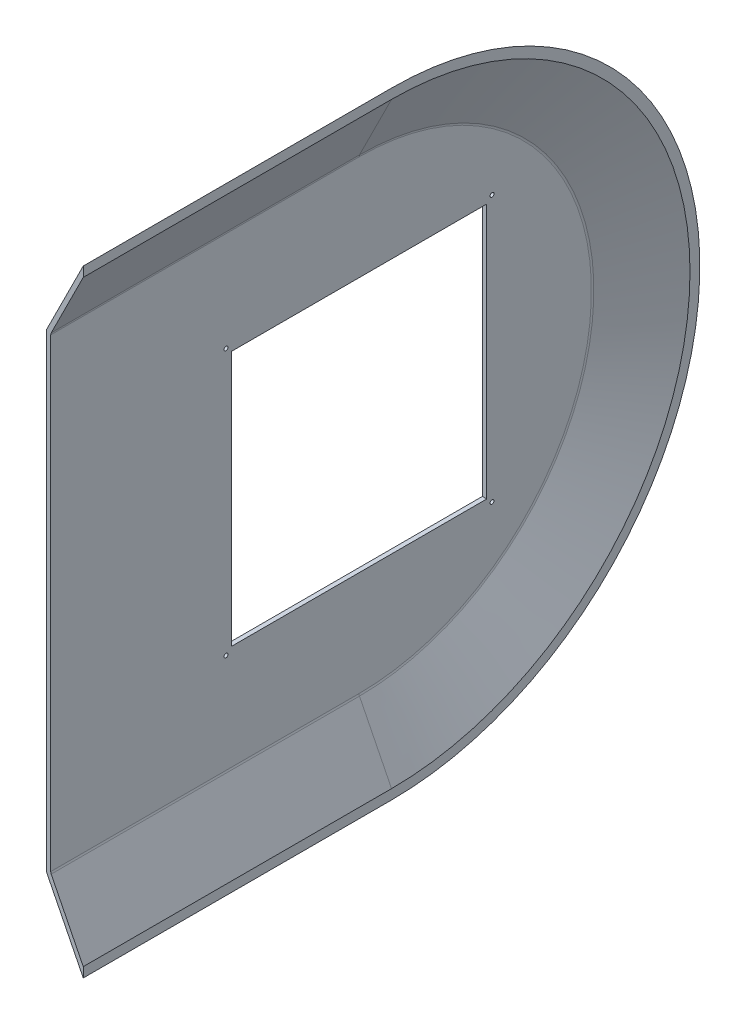
SolidWorks part; units mm, degrees
ref_plane "Plan de face" through (0, 0, 0) normal (0, 0, 1) x (1, 0, 0)
ref_plane "Plan de dessus" through (0, 0, 0) normal (0, 1, 0) x (1, 0, 0)
ref_plane "Plan de droite" through (0, 0, 0) normal (1, 0, 0) x (0, 0, -1)
sketch "Esquisse2" plane through (0, 0, 0) normal (0, 0, 1) x (1, 0, 0)
  line L0 (41.9268, 350) -> (41.9268, 0)
  line L5 (0, 266.1905) -> (41.9268, 350)
  line L6 (41.9268, 0) -> (0, 0)
  line L8 (0, 266.1905) -> (0, 0)
  dimension "D1" = 266.1905
  dimension "D2" = 350
  dimension "D3" = 153.423
  dimension "D4" = 90
revolve "Revolve1" add sketch "Esquisse2" angle 180 about L6
sketch "Sketch5" plane through (0, 0, 0) normal (0, 0, 1) x (1, 0, 0)
  line L3 (41.9268, 350) -> (0, 266.1905) construction
  line L4 (0, 266.1905) -> (41.9268, 350)
  line L5 (0, 266.1905) -> (0, -266.1905)
  line L6 (0, -266.1905) -> (41.9268, -350)
  line L7 (41.9268, -350) -> (41.9268, 350)
extrude "Boss-Extrude1" add sketch "Sketch5" along normal blind 350 contours L5 L6 L7 L4
shell "Shell2" thickness 5 removed face at (41.9268, 0, 87.5) removed face at (20.9634, 0, 350)
sketch "Sketch4" plane through (0, 0, 0) normal (-1, 0, 0) x (0, 0, 1)
  line L0 (0, -55) -> (0, 55) construction
  line L1 (-145, 145) -> (145, 145)
  line L2 (-145, 145) -> (-145, -145)
  line L3 (-145, -145) -> (145, -145)
  line L4 (145, 145) -> (145, -145)
  dimension "D1" = 290
  dimension "D2" = 290
  dimension "D3" = 145
  dimension "D4" = 145
extrude "Cut-Extrude1" cut sketch "Sketch4" against normal through all
sketch "Sketch7" plane through (0, 0, 0) normal (0, 0, 1) x (1, 0, 0)
  line L0 (0, 0) -> (75.7734, 0) construction
sketch "Sketch8" plane through (0, 0, 0) normal (-1, 0, 0) x (0, 0, 1)
  line L1 (-151, 151) -> (151, 151)
  line L2 (-151, 151) -> (-151, -151)
  line L3 (-151, -151) -> (151, -151)
  line L4 (151, 151) -> (151, -151)
  point P4 (0, 151)
  point P6 (151, 0)
  dimension "D1" = 302
  dimension "D2" = 302
  dimension "D3" = 0
  dimension "D4" = 0
hole_wizard "M4 Clearance Hole1" positions "Sketch11" profile "Sketch10" hole size "M4" standard "ANSI Metric"
sketch "Sketch11" plane through (0, 0, 0) normal (-1, 0, 0) x (0, 0, 1)
  point P2 (151, 151)
  point P5 (151, -151)
  point P8 (-151, -151)
  point P11 (-151, 151)
sketch "Sketch10" plane through (0, 151, 151) normal (0, 1, 0) x (0, 0, 1)
  line L0 (0, 0) -> (0, 31.3519)
  line L1 (0, 31.3519) -> (2.25, 30)
  line L2 (2.25, 30) -> (2.25, 0)
  line L5 (2.25, 0) -> (0, 0)
  line L10 (0, 31.3519) -> (-2.25, 30) construction
  line L11 (0, -6.35) -> (0, 107.95) construction
  dimension "Hole Dia." = 4.5
  dimension "Hole Depth" = 30
  dimension "Drill Angle" = 118
fillet "Fillet1" radius 5 6 edges at (5, -265.0097, 175) (5, 0, -265.0097) (5, 265.0097, 175) (0, -266.1905, 175) (0, 0, -266.1905) (0, 266.1905, 175)
equation "\"D3@Sketch4\"=\"D2@Sketch4\"/2"
equation "\"D4@Sketch4\"=\"D1@Sketch4\"/2"
